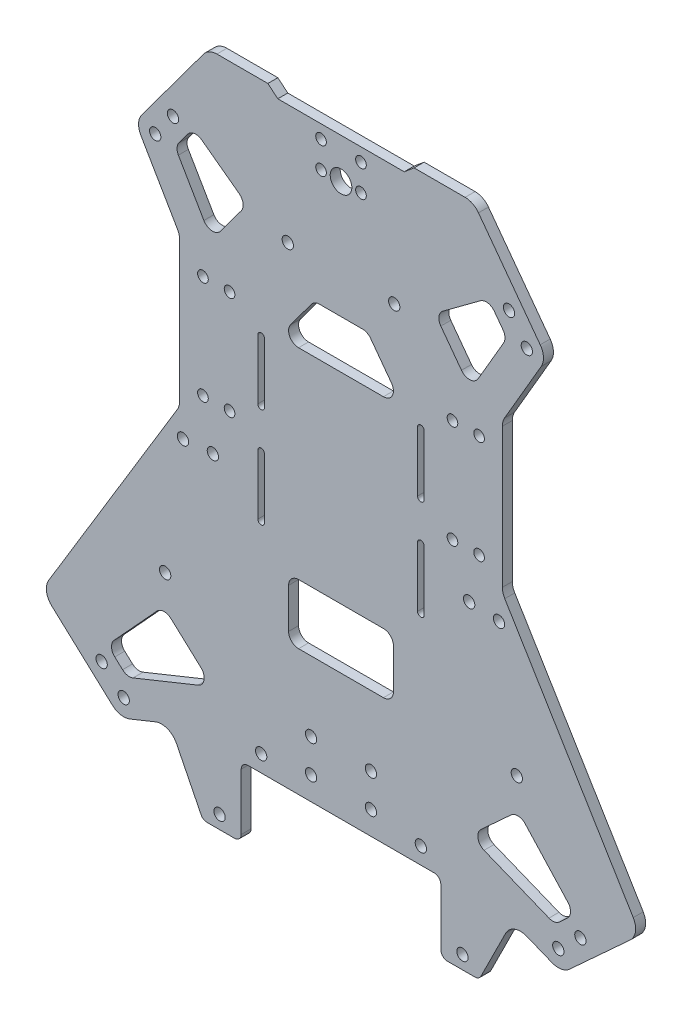
SolidWorks part; units mm, degrees
material "Thornel Mat VMA"
ref_plane "Front Plane" through (0, 0, 0) normal (0, 0, 1) x (1, 0, 0)
ref_plane "Top Plane" through (0, 0, 0) normal (0, 1, 0) x (1, 0, 0)
ref_plane "Right Plane" through (0, 0, 0) normal (1, 0, 0) x (0, 0, -1)
sketch "Sketch1" plane through (0, 0, 0) normal (0, 0, 1) x (1, 0, 0)
  line L0 (0, 0) -> (19, 0)
  line L1 (19, 0) -> (21.9794, 2.5)
  line L2 (21.9794, 2.5) -> (39.8216, 2.5)
  line L3 (39.8216, 2.5) -> (61.83, -27.2427)
  line L4 (61.83, -27.2427) -> (48.5, -50.146)
  line L5 (48.5, -50.146) -> (48.5, -94.8136)
  line L6 (48.5, -94.8136) -> (89.9615, -163.231)
  line L7 (89.9615, -163.231) -> (66.3721, -184.8537)
  line L8 (66.3721, -184.8537) -> (51.5362, -178.8624)
  line L9 (51.5362, -178.8624) -> (41.5, -199)
  line L10 (41.5, -199) -> (30, -199)
  line L11 (30, -199) -> (30, -178)
  line L12 (30, -178) -> (0, -178)
  line L14 (0, 0) -> (0, -178)
  circle A0 centre (6, -4) radius 1.6
  circle A3 centre (41.5, -57.5) radius 1.6
  circle A4 centre (33.5, -57.5) radius 1.6
  circle A5 centre (41.5, -88.5) radius 1.6
  circle A6 centre (33.5, -88.5) radius 1.6
  dimension "D20" = 3.2
  dimension "D35" = 3.2
  dimension "D2" = 2.5
  dimension "D3" = 140
  dimension "D4" = 113.3
  dimension "D5" = 126.5
  dimension "D6" = 37
  dimension "D7" = 30
  dimension "D8" = 26.5
  dimension "D9" = 41.5
  dimension "D10" = 48.5
  dimension "D11" = 80
  dimension "D12" = 178
  dimension "D13" = 32
  dimension "D14" = 115.5
  dimension "D15" = 16
  dimension "D16" = 94.5
  dimension "D17" = 22.5
  dimension "D18" = 116.491
  dimension "D19" = 21
  dimension "D21" = 19
  dimension "D22" = 4
  dimension "D23" = 6
  dimension "D30" = 7
  dimension "D31" = 8
  dimension "D32" = 7.354
  dimension "D33" = 31
extrude "Boss-Extrude1" add sketch "Sketch1" along normal blind 3 contours L14 L12 L11 L10 L9 L8 L7 L6 L5 L4 L3 L2 L1 L0
extrude "Cut-Extrude1" cut sketch "Sketch1<3>" along normal through all contours A0 | A4 | A3 | A6 | A5
sketch "Sketch1<3>" plane through (0, 0, 0) normal (0, 0, 1) x (1, 0, 0) same geometry as "Sketch1"
fillet "Fillet1" radius 5 7 edges at (39.8216, 2.5, 1.5) (51.5362, -178.8624, 1.5) (66.3721, -184.8537, 1.5) (89.9615, -163.231, 1.5) (48.5, -94.8136, 1.5) (48.5, -50.146, 1.5) (61.83, -27.2427, 1.5)
fillet "Fillet2" radius 2 3 edges at (30, -178, 1.5) (30, -199, 1.5) (41.5, -199, 1.5)
hole_wizard "M3 Clearance Hole2" positions "Sketch6" profile "Sketch7" hole size "M3" standard "ANSI Metric" end condition up to next
sketch "Sketch6" plane through (0, 0, 3) normal (0, 0, 1) x (1, 0, 0)
  line L0 (71.9537, -172.9547) -> (65.3192, -179.0361) construction
  line L2 (86.9389, -166.0016) -> (68.6977, -182.722) construction
  line L3 (71.9537, -172.9547) -> (77.851, -167.5491) construction
  line L7 (52.8498, -140.2738) -> (55.4731, -103.367) construction
  line L9 (52.8498, -140.2738) -> (77.851, -167.5491) construction
  line L11 (55.4731, -103.367) -> (47.4932, -102.7998) construction
  line L12 (47.4932, -102.7998) -> (38.5159, -102.1616) construction
  line L13 (47.4932, -102.7998) -> (51.7693, -100.2084) construction
  line L14 (49.2239, -96.0081) -> (87.8365, -159.7244) construction
  line L15 (50.5, -20.3369) -> (55.8534, -27.5716) construction
  line L17 (41.3207, 0.4741) -> (59.8727, -24.5975) construction
  line L18 (50.5, -20.3369) -> (45.7414, -13.9061) construction
  line L20 (45.7414, -13.9061) -> (15.9987, -35.9145) construction
  point P0 (65.3192, -179.0361)
  point P3 (71.9537, -172.9547)
  point P23 (52.8498, -140.2738)
  point P34 (47.4932, -102.7998)
  point P36 (38.5159, -102.1616)
  point P48 (55.8534, -27.5716)
  point P51 (50.5, -20.3369)
  point P66 (15.9987, -35.9145)
  dimension "D1" = 9
  dimension "D2" = 37
  dimension "D3" = 8
  dimension "D4" = 5
sketch "Sketch7" plane through (65.3192, -179.0361, 3) normal (1, 0, 0) x (0, -1, 0)
  line L0 (0, 0) -> (0, 3.001)
  line L1 (0, 3.001) -> (1.7, 3.001)
  line L2 (1.7, 3.001) -> (1.7, 0)
  line L5 (1.7, 0) -> (0, 0)
  line L11 (0, -6.35) -> (0, 107.95) construction
  dimension "Thru Hole Dia." = 3.4
  dimension "Thru Hole Depth" = 3.001
hole_wizard "M3 Clearance Hole3" positions "Sketch8" profile "Sketch9" hole size "M3" standard "ANSI Metric" end condition up to next
sketch "Sketch8" plane through (0, 0, 3) normal (0, 0, 1) x (1, 0, 0)
  line L0 (9, -171) -> (9, -178) construction
  line L1 (28, -178) -> (0, -178) construction
  line L3 (24, -173) -> (24, -178) construction
  line L5 (9, -171) -> (9, -161) construction
  line L6 (30, -197) -> (30, -180) construction
  line L7 (40.2621, -199) -> (32, -199) construction
  line L8 (0, 0) -> (0, -178) construction
  point P0 (9, -171)
  point P2 (24, -173)
  point P15 (9, -161)
  point P19 (36.5, -195)
  dimension "D1" = 5
  dimension "D2" = 7
  dimension "D3" = 9
  dimension "D4" = 24
  dimension "D5" = 10
  dimension "D6" = 6.5
  dimension "D7" = 4
sketch "Sketch9" plane through (9, -171, 3) normal (1, 0, 0) x (0, -1, 0)
  line L0 (0, 0) -> (0, 3.001)
  line L1 (0, 3.001) -> (1.7, 3.001)
  line L2 (1.7, 3.001) -> (1.7, 0)
  line L5 (1.7, 0) -> (0, 0)
  line L11 (0, -6.35) -> (0, 107.95) construction
  dimension "Thru Hole Dia." = 3.4
  dimension "Thru Hole Depth" = 3.001
mirror "Mirror2" about plane through (0, 0, 3) normal (1, 0, 0) of "M3 Clearance Hole3", "Cut-Extrude1", "Boss-Extrude1", "Fillet1", "Fillet2", "M3 Clearance Hole2"
hole_wizard "Ø2.0 (2) Diameter Slot1" positions "Sketch10" profile "Sketch11" size "Ø2.0" standard "ANSI Metric" slot yes end condition up to next
sketch "Sketch10" plane through (0, 0, 3) normal (0, 0, 1) x (1, 0, 0)
  line L0 (24, -113.4168) -> (24, -93.4168) construction
  line L1 (24, -103.4168) -> (-24, -103.4168) construction
  line L3 (0, 0) -> (0, -50000) construction
  line L4 (24, -73.4168) -> (24, -93.4168) construction
  line L7 (-24, -73.4168) -> (-24, -103.4168) construction
  line L9 (24, -73.4168) -> (-24, -73.4168) construction
  line L12 (24, -93.4168) -> (48.5, -93.4168) construction
  point P0 (24, -103.4168)
  point P7 (-24, -103.4168)
  point P16 (0, -103.4168)
  point P17 (24, -73.4168)
  point P19 (-24, -73.4168)
  dimension "D1" = 20
  dimension "D2" = 48
  dimension "D3" = 30
sketch "Sketch11" plane through (24, -103.4168, 3) normal (1, 0, 0) x (0, -1, 0)
  line L0 (0, 0) -> (0, 3)
  line L1 (0, 3) -> (1, 3)
  line L2 (1, 3) -> (1, 0)
  line L5 (1, 0) -> (0, 0)
  line L11 (0, -6.35) -> (0, 107.95) construction
  dimension "Thru Hole Dia." = 2
  dimension "Thru Hole Depth" = 3
sketch "Sketch12" plane through (0, 0, 3) normal (0, 0, 1) x (1, 0, 0)
  line L0 (0, 0) -> (0, -50000) construction
  line L7 (-41.8818, -22.1395) -> (-30.6278, -30.467)
  line L12 (41.216, -42.7812) -> (48.8836, -29.6069)
  line L19 (48.7024, -26.3134) -> (46.0779, -22.7666)
  line L20 (41.8818, -22.1395) -> (30.6278, -30.467)
  line L21 (30.0007, -34.663) -> (36.2116, -43.0566)
  line L22 (41.3207, 0.4741) -> (59.8727, -24.5975) construction
  line L23 (60.1748, -30.0867) -> (49.1786, -48.98) construction
  line L24 (48.8836, -29.6069) -> (57.5264, -34.6371) construction
  line L25 (48.7024, -26.3134) -> (56.7409, -20.3652) construction
  line L26 (-48.7024, -26.3134) -> (-46.0779, -22.7666)
  line L27 (-41.216, -42.7812) -> (-48.8836, -29.6069)
  line L28 (-30.0007, -34.663) -> (-36.2116, -43.0566)
  line L29 (65.6616, -171.9396) -> (68.0078, -169.7889)
  line L30 (68.1922, -165.5503) -> (55.3537, -151.5441)
  line L31 (51.1151, -151.3597) -> (42.0882, -159.634)
  line L32 (42.992, -164.6272) -> (62.5111, -172.5098)
  line L33 (63.4469, -183.6723) -> (55.8219, -180.5931) construction
  line L34 (86.9389, -166.0016) -> (68.6977, -182.722) construction
  line L35 (65.6616, -171.9396) -> (72.4187, -179.3112) construction
  line L36 (62.5111, -172.5098) -> (58.7665, -181.7822) construction
  line L37 (-51.1151, -151.3597) -> (-42.0882, -159.634)
  line L38 (-68.1922, -165.5503) -> (-55.3537, -151.5441)
  line L39 (-65.6616, -171.9396) -> (-68.0078, -169.7889)
  line L40 (-42.992, -164.6272) -> (-62.5111, -172.5098)
  line L43 (6, -12) -> (-6, -12) construction
  line L54 (6.4879, -47.2107) -> (-6.4879, -47.2107)
  line L55 (-8.8994, -48.4262) -> (-15.1665, -56.8957)
  line L56 (-12.7549, -61.6801) -> (12.7549, -61.6801)
  line L57 (15.1665, -56.8957) -> (8.8994, -48.4262)
  line L58 (28.2162, -32.2515) -> (8, -47.2107) construction
  line L59 (18.7068, -61.6801) -> (38.9231, -46.7209) construction
  line L64 (12.7549, -58.6801) -> (12.7549, -125.0185) construction
  line L65 (-12.7549, -140.0185) -> (12.7549, -140.0185)
  line L66 (-15.7549, -137.0185) -> (-15.7549, -125.0185)
  line L67 (-12.7549, -122.0185) -> (12.7549, -122.0185)
  line L68 (15.7549, -137.0185) -> (15.7549, -125.0185)
  line L69 (-15.7549, -140.0185) -> (15.7549, -122.0185) construction
  line L70 (-15.7549, -122.0185) -> (15.7549, -140.0185) construction
  line L71 (12.7549, -137.0185) -> (38.5832, -162.8468) construction
  arc A8 (-46.0779, -22.7666) -> (-41.8818, -22.1395) centre (-43.6663, -24.551) cw
  arc A13 (6.4879, -47.2107) -> (8.8994, -48.4262) centre (6.4879, -50.2107) cw
  arc A15 (41.216, -42.7812) -> (36.2116, -43.0566) centre (38.6232, -41.2721) cw
  arc A16 (30.6278, -30.467) -> (30.0007, -34.663) centre (32.4123, -32.8786) ccw
  arc A17 (46.0779, -22.7666) -> (41.8818, -22.1395) centre (43.6663, -24.551) ccw
  arc A18 (48.8836, -29.6069) -> (48.7024, -26.3134) centre (46.2908, -28.0979) ccw
  arc A19 (-48.8836, -29.6069) -> (-48.7024, -26.3134) centre (-46.2908, -28.0979) cw
  arc A20 (-41.216, -42.7812) -> (-36.2116, -43.0566) centre (-38.6232, -41.2721) ccw
  arc A21 (-30.6278, -30.467) -> (-30.0007, -34.663) centre (-32.4123, -32.8786) cw
  arc A22 (65.6616, -171.9396) -> (62.5111, -172.5098) centre (63.6344, -169.7281) cw
  arc A23 (68.0078, -169.7889) -> (68.1922, -165.5503) centre (65.9807, -167.5774) ccw
  arc A24 (55.3537, -151.5441) -> (51.1151, -151.3597) centre (53.1422, -153.5712) ccw
  arc A25 (42.0882, -159.634) -> (42.992, -164.6272) centre (44.1153, -161.8455) ccw
  arc A26 (-55.3537, -151.5441) -> (-51.1151, -151.3597) centre (-53.1422, -153.5712) cw
  arc A27 (-68.0078, -169.7889) -> (-68.1922, -165.5503) centre (-65.9807, -167.5774) cw
  arc A28 (-65.6616, -171.9396) -> (-62.5111, -172.5098) centre (-63.6344, -169.7281) ccw
  arc A29 (-42.0882, -159.634) -> (-42.992, -164.6272) centre (-44.1153, -161.8455) cw
  circle A37 centre (0, -12) radius 3.25
  circle A38 centre (6, -12) radius 1.6
  circle A39 centre (-6, -12) radius 1.6
  arc A40 (-6.4879, -47.2107) -> (-8.8994, -48.4262) centre (-6.4879, -50.2107) ccw
  arc A41 (-15.1665, -56.8957) -> (-12.7549, -61.6801) centre (-12.7549, -58.6801) ccw
  arc A42 (12.7549, -61.6801) -> (15.1665, -56.8957) centre (12.7549, -58.6801) ccw
  arc A43 (12.7549, -140.0185) -> (15.7549, -137.0185) centre (12.7549, -137.0185) ccw
  arc A44 (-12.7549, -140.0185) -> (-15.7549, -137.0185) centre (-12.7549, -137.0185) cw
  arc A45 (-15.7549, -125.0185) -> (-12.7549, -122.0185) centre (-12.7549, -125.0185) cw
  arc A46 (12.7549, -122.0185) -> (15.7549, -125.0185) centre (12.7549, -125.0185) cw
  point P6 (0, -47.2107)
  point P12 (0, -131.0185)
  point P22 (-8, -47.2107)
  point P54 (38.9231, -46.7209)
  point P57 (28.2162, -32.2515)
  point P60 (44.2934, -20.355)
  point P89 (70.2193, -167.7618)
  point P92 (53.3266, -149.3326)
  point P95 (38.5832, -162.8468)
  dimension "D3" = 12
  dimension "D7" = 18
  dimension "D4" = 3.2
  dimension "D11" = 3
  dimension "D15" = 3
  dimension "D2" = 6.5
  dimension "D6" = 3
  dimension "D8" = 3
  dimension "D5" = 16
  dimension "D9" = 20
  dimension "D10" = 18
  dimension "D12" = 10
  dimension "D13" = 25
  dimension "D14" = 20
  dimension "D16" = 12
extrude "Cut-Extrude2" cut sketch "Sketch12" against normal up to next
